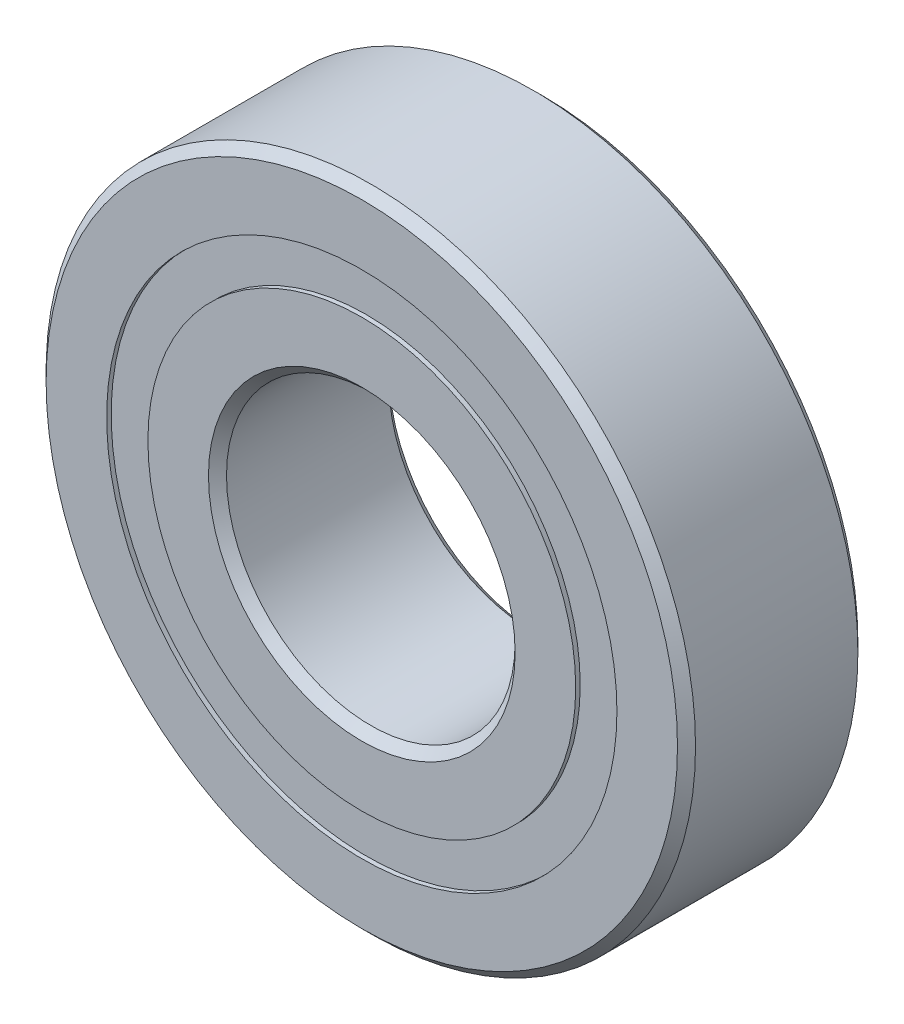
SolidWorks part; units mm, degrees
ref_plane "Front Plane" through (0, 0, 0) normal (0, 0, 1) x (1, 0, 0)
ref_plane "Top Plane" through (0, 0, 0) normal (0, 1, 0) x (1, 0, 0)
ref_plane "Right Plane" through (0, 0, 0) normal (1, 0, 0) x (0, 0, -1)
sketch "Sketch1" plane through (0, 0, 0) normal (1, 0, 0) x (0, 0, -1)
  line L0 (-3.9688, 0) -> (3.9688, 0) construction
  line L1 (0, 14.2875) -> (0, -14.2875) construction
  line L2 (3.5719, 14.2875) -> (-3.5719, 14.2875)
  line L3 (-3.5719, 14.2875) -> (-3.9688, 13.8906)
  line L4 (-3.9688, 13.8906) -> (-3.9688, 11.2259)
  line L5 (-3.9688, 11.2259) -> (-1.7639, 11.2259)
  line L6 (3.9688, 11.2259) -> (1.7639, 11.2259)
  line L7 (3.9688, 13.8906) -> (3.9688, 11.2259)
  line L8 (3.5719, 14.2875) -> (3.9688, 13.8906)
  line L9 (0, 14.2875) -> (0, 10.3187) construction
  line L10 (0, 10.3187) -> (0, 6.35) construction
  arc A0 (-1.7639, 11.2259) -> (1.7639, 11.2259) centre (0, 10.3187) cw
  point P14 (0, 6.35)
  dimension "Width" = 7.9375
  dimension "OD" = 28.575
  dimension "D1" = 45
  dimension "D2" = 0.3969
  dimension "Shaft Dia" = 12.7
  dimension "D3" = 3.5278
  dimension "D4" = 0.9071
revolve "Revolve1" add sketch "Sketch1" angle 360 about L0
sketch "Sketch3" plane through (0, 0, 0) normal (1, 0, 0) x (0, 0, -1)
  line L0 (-3.9688, 9.4116) -> (-1.7639, 9.4116)
  line L1 (0, 14.2875) -> (0, -14.2875) construction
  line L2 (-3.9688, 13.8906) -> (-3.9688, 11.2259) construction
  line L3 (-3.9688, 9.4116) -> (-3.9688, 6.7469)
  line L4 (-3.5719, 14.2875) -> (-3.9688, 13.8906) construction
  line L5 (-3.9688, 6.7469) -> (-3.5719, 6.35)
  line L6 (-3.5719, 6.35) -> (3.5719, 6.35)
  line L7 (3.5719, 14.2875) -> (3.5719, -14.2875) construction
  line L8 (3.5719, 6.35) -> (3.9688, 6.7469)
  line L9 (3.9688, -13.8906) -> (3.9688, 13.8906) construction
  line L10 (3.9688, 6.7469) -> (3.9688, 9.4116)
  line L11 (3.9688, 9.4116) -> (1.7639, 9.4116)
  line L13 (3.5719, 14.2875) -> (3.9688, 13.8906) construction
  arc A0 (1.7639, 11.2259) -> (-1.7639, 11.2259) centre (0, 10.3187) ccw construction
  arc A1 (1.7639, 9.4116) -> (-1.7639, 9.4116) centre (0, 10.3187) cw
revolve "Revolve3" add sketch "Sketch3" angle 360 about L0
sketch "Sketch4" plane through (0, 0, 0) normal (1, 0, 0) x (0, 0, -1)
  line L0 (-1.9835, 10.3187) -> (1.9835, 10.3187)
  arc A2 (-1.9835, 10.3187) -> (1.9835, 10.3187) centre (0, 10.3187) cw
  arc A3 (1.7639, 11.2259) -> (-1.7639, 11.2259) centre (0, 10.3187) ccw construction
revolve "Revolve4" add sketch "Sketch4" angle 360 about L0
ref_axis "Axis1" through (0, 0, -3.9688) along (0, 0, 1)
pattern_circular "CirPattern1" count 10 every 36 about axis through (0, 0, -3.9688) along (0, 0, 1) of bodies 104
sketch "Sketch5" plane through (0, 0, 0) normal (1, 0, 0) x (0, 0, -1)
  line L0 (-3.9688, 11.2259) -> (-1.7639, 11.2259) construction
  line L1 (-3.7703, 11.2259) -> (-1.9835, 11.2259)
  line L2 (-3.7703, 11.2259) -> (-3.7703, 9.4116)
  line L3 (-3.7703, 9.4116) -> (-1.9835, 9.4116)
  line L4 (-1.9835, 11.2259) -> (-1.9835, 9.4116)
  line L5 (-3.9688, 9.4116) -> (-1.7639, 9.4116) construction
  line L6 (3.9688, 11.2259) -> (1.7639, 11.2259) construction
  line L7 (3.7703, 11.2259) -> (1.9835, 11.2259)
  line L8 (3.7703, 11.2259) -> (3.7703, 9.4116)
  line L9 (3.7703, 9.4116) -> (1.9835, 9.4116)
  line L10 (1.9835, 11.2259) -> (1.9835, 9.4116)
  line L11 (3.9688, 9.4116) -> (1.7639, 9.4116) construction
  line L12 (-3.5719, 14.2875) -> (-3.9688, 13.8906) construction
  point P18 (-3.7703, 14.0891)
revolve "Revolve5" add sketch "Sketch5" angle 360 about L0
equation "\"D2@Sketch1\" = \"Width@Sketch1\"*.05"
equation "\"D3@Sketch1\" = \"Width@Sketch1\"/2.25"
equation "\"D4@Sketch1\" = (((\"OD@Sketch1\"-\"Width@Sketch1\")/2)/3.25)/3.5"
equation "\"D2@CirPattern1\" = 360/\"Balls@CirPattern1\""
